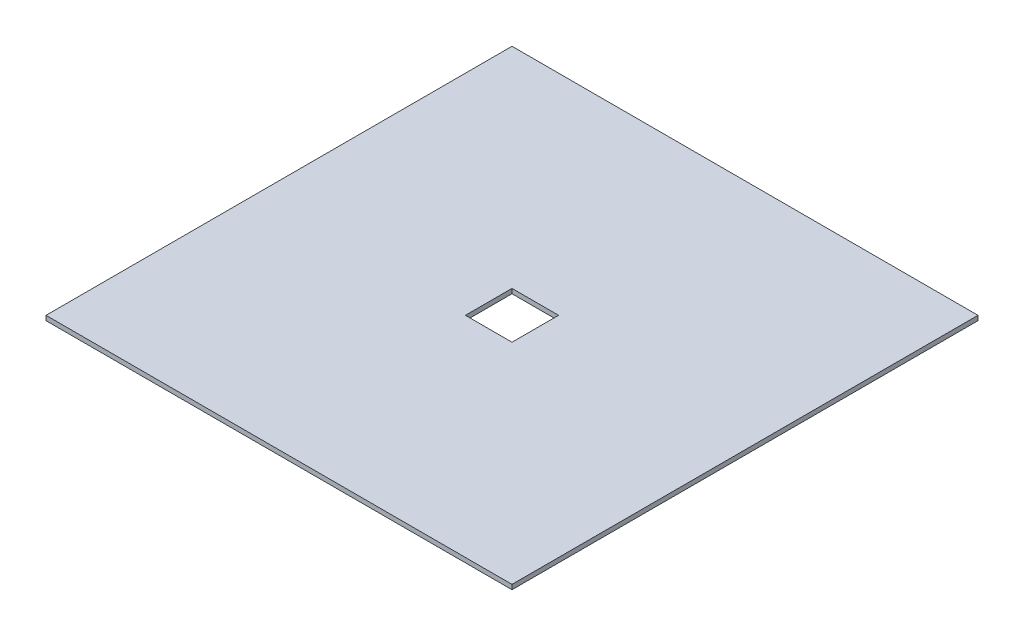
SolidWorks part; units mm, degrees
material "Acrylic (Medium-high impact)"
ref_plane "Front Plane" through (0, 0, 0) normal (0, 0, 1) x (1, 0, 0)
ref_plane "Top Plane" through (0, 0, 0) normal (0, 1, 0) x (1, 0, 0)
ref_plane "Right Plane" through (0, 0, 0) normal (1, 0, 0) x (0, 0, -1)
sketch "Sketch2" plane through (0, 0, 0) normal (0, 1, 0) x (1, 0, 0)
  line L1 (-250, 250) -> (250, 250)
  line L2 (-250, 250) -> (-250, -250)
  line L3 (-250, -250) -> (250, -250)
  line L4 (250, 250) -> (250, -250)
  line L5 (-250, 250) -> (250, -250) construction
  line L6 (-250, -250) -> (250, 250) construction
  point P0 (0, 0)
  dimension "D1" = 500
  dimension "D2" = 500
extrude "Boss-Extrude1" add sketch "Sketch2" along normal blind 5 contours L1 L4 L3 L2
sketch "Sketch3" plane through (0, 0, 0) normal (0, 1, 0) x (1, 0, 0)
  line L1 (-25, -25) -> (25, -25)
  line L2 (-25, -25) -> (-25, 25)
  line L3 (-25, 25) -> (25, 25)
  line L4 (25, -25) -> (25, 25)
  line L5 (-25, -25) -> (25, 25) construction
  line L6 (-25, 25) -> (25, -25) construction
  point P0 (0, 0)
  dimension "D1" = 50
  dimension "D2" = 50
extrude "Cut-Extrude5" cut sketch "Sketch3" against normal blind 5 and the other way blind 5
